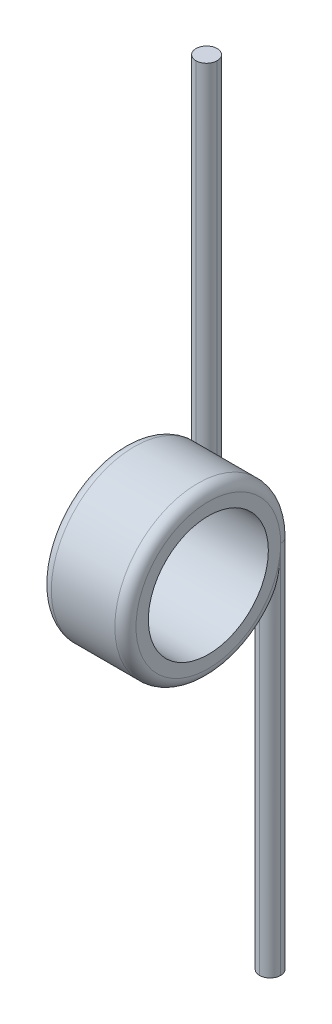
SolidWorks part; units mm, degrees
ref_plane "Plan de face" through (0, 0, 0) normal (0, 0, 1) x (1, 0, 0)
ref_plane "Plan de dessus" through (0, 0, 0) normal (0, 1, 0) x (1, 0, 0)
ref_plane "Plan de droite" through (0, 0, 0) normal (1, 0, 0) x (0, 0, -1)
sketch "Sketch2" plane through (0, 0, 0) normal (1, 0, 0) x (0, 0, -1)
  line L0 (2.35, 0) -> (2.35, 10.9423)
  line L1 (2.35, 10.9423) -> (1.75, 10.9423)
  line L2 (1.75, 1.5684) -> (1.75, 10.9423)
  line L3 (2.35, 0) -> (2.35, -10.6015)
  line L4 (1.75, -1.5684) -> (1.75, -10.6015)
  line L5 (1.75, 0) -> (1.75, 10.9423) construction
  line L6 (1.75, -10.6015) -> (2.35, -10.6015)
  line L8 (1.75, 0) -> (1.75, -10.6015) construction
  circle A0 centre (0, 0) radius 2.35
  circle A1 centre (0, 0) radius 1.7
  point P10 (-1.75, 0)
  point P11 (-1.75, -7.0103)
  dimension "D1" = 4.7
  dimension "D2" = 3.4
  dimension "D3" = 0.6
  dimension "D4" = 0.6
extrude "Boss-Extrude1" add sketch "Sketch2" along normal blind 2.4 contours A0 L0 L1 L2 | A0 A1 | A0 L4 L6 L3 region at (0, 6.0022, -2.0562) region at (0, -0.8159, -2.1328) region at (0, -5.8316, -2.0565)
sketch "Sketch3" plane through (2.4, 0, 0) normal (1, 0, 0) x (0, 0, -1)
  line L5 (1.75, 10.9423) -> (1.75, 1.5684)
  line L6 (1.75, -1.5684) -> (1.75, -10.6015)
  line L7 (1.75, -10.6015) -> (2.35, -10.6015)
  line L8 (2.35, -10.6015) -> (2.35, 10.9423)
  line L9 (2.35, 10.9423) -> (1.75, 10.9423)
  line L10 (1.75, 10.9423) -> (1.75, 1.5684)
  line L11 (1.75, -1.5684) -> (1.75, -10.6015)
  line L12 (1.75, -10.6015) -> (2.35, -10.6015)
  line L13 (2.35, -10.6015) -> (2.35, 10.9423)
  line L14 (2.35, 10.9423) -> (1.75, 10.9423)
  circle A0 centre (0, 0) radius 2.35
  arc A2 (1.75, 1.5684) -> (1.75, -1.5684) centre (0, 0) ccw
  arc A3 (1.75, 1.5684) -> (1.75, -1.5684) centre (0, 0) ccw
  line M7 (1.75, 10.9423) -> (1.75, 1.5684)
  line M12 (2.35, 10.9423) -> (1.75, 10.9423)
  dimension "D1" = 0
extrude "Cut-Extrude1" cut sketch "Sketch3" against normal blind 1.8 contours A0 L13 M12 M7 region at (2.4, 6.0022, -2.0562)
sketch "Sketch4" plane through (0, 0, 0) normal (-1, 0, 0) x (0, 0, 1)
  line L5 (-1.75, 1.5684) -> (-1.75, 10.9423)
  line L6 (-1.75, 1.5684) -> (-1.75, 10.9423)
  line L7 (-2.35, 10.9423) -> (-2.35, -10.6015)
  line L8 (-2.35, -10.6015) -> (-1.75, -10.6015)
  line L9 (-1.75, -10.6015) -> (-1.75, -1.5684)
  line L10 (-1.75, 10.9423) -> (-2.35, 10.9423)
  line L11 (-1.75, 10.9423) -> (-2.35, 10.9423)
  line L12 (-2.35, 10.9423) -> (-2.35, -10.6015)
  line L13 (-2.35, -10.6015) -> (-1.75, -10.6015)
  line L14 (-1.75, -10.6015) -> (-1.75, -1.5684)
  circle A0 centre (0, 0) radius 2.35
  arc A2 (-1.75, -1.5684) -> (-1.75, 1.5684) centre (0, 0) ccw
  arc A3 (-1.75, -1.5684) -> (-1.75, 1.5684) centre (0, 0) ccw
  line M10 (-2.35, -10.6015) -> (-1.75, -10.6015)
  line M11 (-1.75, -10.6015) -> (-1.75, -1.5684)
  dimension "D1" = 0
extrude "Cut-Extrude2" cut sketch "Sketch4" against normal blind 1.8 contours A0 L12 M10 M11 region at (0, -5.8316, -2.0565)
fillet "Fillet1" radius 0.3 10 edges at (2.4, 0.8396, 2.1949) (0, -0.8396, 2.1949) (2.4, -5.3008, -2.35) (1.8, -5.3008, -2.35) (1.8, -6.085, -1.75) (2.4, -6.085, -1.75) (0.6, 6.2553, -1.75) (0, 6.2553, -1.75) (0, 5.4711, -2.35) (0.6, 5.4711, -2.35)
